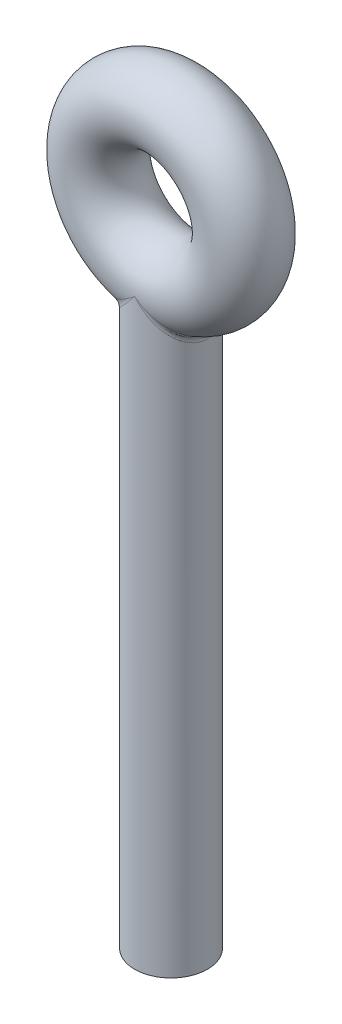
SolidWorks part; units mm, degrees
ref_plane "Front Plane" through (0, 0, 0) normal (0, 0, 1) x (1, 0, 0)
ref_plane "Top Plane" through (0, 0, 0) normal (0, 1, 0) x (1, 0, 0)
ref_plane "Right Plane" through (0, 0, 0) normal (1, 0, 0) x (0, 0, -1)
sketch "Sketch1" plane through (0, 0, 0) normal (0, 0, 1) x (1, 0, 0)
  circle A0 centre (0, 0) radius 19.05
  dimension "D1" = 38.1
sketch "Sketch2" plane through (0, 0, 0) normal (1, 0, 0) x (0, 0, -1)
  circle A0 centre (0, 19.05) radius 9.525
  dimension "D1" = 19.05
ref_axis "Axis1" through (0, 0, -88.99) along (0, 0, 1)
revolve "Revolve1" add sketch "Sketch2" angle 360 about axis through (0, 0, -88.99) along (0, 0, 1)
ref_plane "Plane1" through (0, -19.05, 0) normal (0, 1, 0) x (-1, 0, 0)
sketch "Sketch3" plane through (0, -19.05, 0) normal (0, 1, 0) x (-1, 0, 0)
  circle A0 centre (0, 0) radius 9.525
  dimension "D1" = 19.05
extrude "Boss-Extrude1" add sketch "Sketch3" against normal blind 152.4
fillet "Fillet1" radius 2.54 2 edges at (9.4696, -26.9015, 1.0262) (-9.4696, -26.9015, -1.0262)
